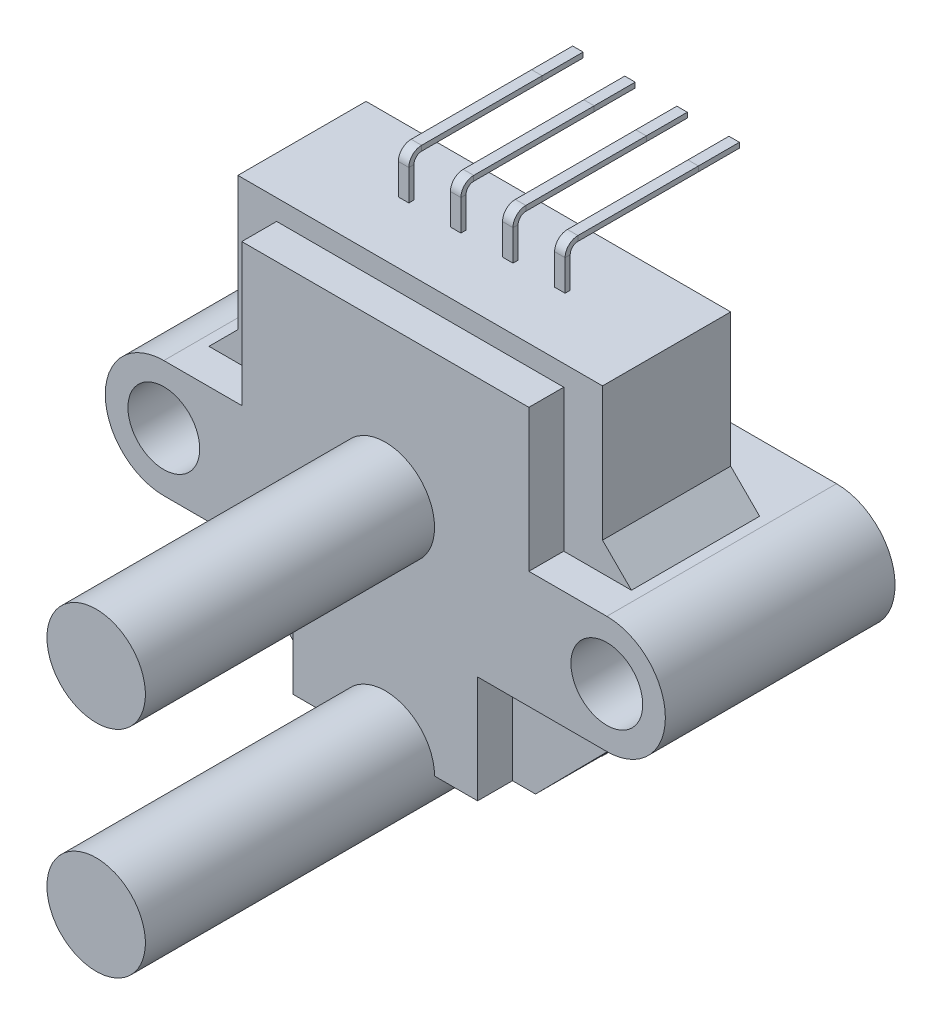
SolidWorks part; units mm, degrees
ref_plane "Front Plane" through (0, 0, 0) normal (0, 0, 1) x (1, 0, 0)
ref_plane "Top Plane" through (0, 0, 0) normal (0, 1, 0) x (1, 0, 0)
ref_plane "Right Plane" through (0, 0, 0) normal (1, 0, 0) x (0, 0, -1)
sketch "Sketch1" plane through (0, 0, 0) normal (0, 0, -1) x (1, 0, 0)
  line L0 (-7.62, 0) -> (-5.08, 0) construction
  line L1 (-5.08, 0) -> (-2.54, 0) construction
  line L2 (-2.54, 0) -> (0, 0) construction
  line L3 (-12.7, 2) -> (5.08, 2)
  line L4 (-3.81, 0) -> (-3.81, 2) construction
  line L5 (-3.81, 2) -> (-3.81, 12.78) construction
  line L6 (-14.61, 12.78) -> (6.99, 12.78) construction
  line L7 (-14.61, 12.78) -> (6.99, 12.78) construction
  line L8 (-14.61, 15.635) -> (6.99, 15.635)
  line L9 (-14.61, 9.925) -> (6.99, 9.925)
  line L10 (5.08, 2) -> (5.08, 8.515)
  line L11 (5.08, 8.515) -> (6.49, 9.925)
  line L12 (6.99, 15.635) -> (-0.9654, 23.6822)
  line L13 (-6.6546, 23.6822) -> (-14.61, 15.635)
  line L14 (-3.81, 12.78) -> (-3.81, 24.87) construction
  line L15 (-12.7, 8.515) -> (-14.11, 9.925)
  line L16 (-12.7, 2) -> (-12.7, 8.515)
  line L17 (-3.81, 20.87) -> (-3.81, 10.37) construction
  line L18 (0.19, 20.87) -> (0.19, 10.37)
  line L19 (-7.81, 20.87) -> (-7.81, 10.37)
  line L20 (-9.4347, 20.87) -> (1.8147, 20.87)
  circle A0 centre (-14.61, 12.78) radius 1.75
  circle A1 centre (6.99, 12.78) radius 1.75
  arc A2 (-14.61, 15.635) -> (-14.61, 9.925) centre (-14.61, 12.78) ccw
  arc A3 (6.99, 9.925) -> (6.99, 15.635) centre (6.99, 12.78) ccw
  arc A4 (-0.9654, 23.6822) -> (-6.6546, 23.6822) centre (-3.81, 20.87) ccw
  circle A5 centre (-3.81, 20.87) radius 2.4
  circle A6 centre (-3.81, 10.37) radius 2.4
  arc A7 (0.19, 20.87) -> (-7.81, 20.87) centre (-3.81, 20.87) ccw
  arc A8 (-7.81, 10.37) -> (0.19, 10.37) centre (-3.81, 10.37) ccw
  point P0 (0, 0)
  point P1 (-5.08, 0)
  point P3 (-2.54, 0)
  point P4 (0, 0)
  point P17 (-3.81, 12.78)
  point P19 (-3.81, 12.78)
  point P34 (-3.81, 15.62)
  dimension "D3" = 3.5
  dimension "D5" = 27.31
  dimension "D11" = 4
  dimension "D12" = 4.8
  dimension "D1" = 2.54
  dimension "D2" = 2
  dimension "D4" = 21.6
  dimension "D6" = 22.87
  dimension "D7" = 12.09
  dimension "D8" = 17.78
  dimension "D9" = 135
  dimension "D10" = 0.5
  dimension "D13" = 10.5
extrude "Boss-Extrude1" add sketch "Sketch1" against normal blind 3.25 contours L9 A8 L18 L8 A3 A1 | A8 L19 L8 L18 L9 | A7 L18 L8 L19 A4 | A8 L9 | L19 A8 L9 A2 L8 A0 | A7 L20 A4 | A5 L20 | A5 L20 | A6 L9 | A6 L9 region at (-11.8365, -12.7798, 0) region at (4.2165, -12.7798, 0) region at (-3.81, -13.3075, 0) region at (-6.9768, -9.8379, 0) region at (-3.81, -11.1528, 0) region at (-3.81, -9.107, 0) region at (-3.81, -17.8119, 0) region at (-7.4272, -22.3561, 0) region at (-3.81, -21.8886, 0) region at (-3.81, -19.8514, 0)
extrude "Boss-Extrude3" add sketch "Sketch1<4>" against normal blind 6.25 from surface contours L18 A7 L12 L8 | L9 A8 L18 L8 A3 A1 | A7 L18 L8 L19 A4 | A8 L9 | A8 L19 L8 L18 L9 | L19 A8 L9 A2 L8 A0 | L13 A7 L19 L8 | L9 A8 L11 L10 L3 L16 L15 | A5 L20 | A6 L9 | A6 L9 region at (-3.81, -5.5809, 0) region at (-11.8365, -12.7798, 0) region at (4.2165, -12.7798, 0) region at (-3.81, -13.3075, 0) region at (-6.9768, -9.8379, 0) region at (-10.1811, -17.7165, 0) region at (-3.81, -11.1528, 0) region at (-3.81, -9.107, 0) region at (2.5611, -17.7165, 0) region at (-3.81, -17.8119, 0) region at (-3.81, -19.8514, 0) starting at face at (-3.81, -14.4425, 3.25)
sketch "Sketch1<4>" plane through (0, 0, 0) normal (0, 0, -1) x (1, 0, 0) same geometry as "Sketch1"
sketch "Sketch3" plane through (0, 0, 9.5) normal (0, 0, 1) x (1, 0, 0)
  line L0 (3.19, -3) -> (-10.81, -3)
  line L1 (-14.11, -9.925) -> (6.49, -9.925)
  line L2 (6.99, -15.635) -> (-14.61, -15.635)
  line L3 (-10.81, -3) -> (-10.81, -9.925)
  line L4 (3.19, -3) -> (3.19, -9.925)
  line L5 (-8.31, -20.87) -> (0.69, -20.87)
  line L6 (0.69, -20.87) -> (0.69, -15.635)
  line L7 (-8.31, -20.87) -> (-8.31, -15.635)
  line L8 (-3.81, -2) -> (-3.81, -12.78) construction
  line L9 (6.49, -9.925) -> (5.08, -8.515)
  line L10 (5.08, -8.515) -> (5.08, -2)
  line L11 (5.08, -2) -> (-12.7, -2)
  line L12 (-12.7, -2) -> (-12.7, -8.515)
  line L13 (-12.7, -8.515) -> (-14.11, -9.925)
  line L14 (-14.11, -9.925) -> (-14.61, -9.925)
  line L15 (-14.61, -15.635) -> (-9.4347, -20.87)
  line L16 (1.8147, -20.87) -> (6.99, -15.635)
  line L17 (6.99, -9.925) -> (6.49, -9.925)
  line L18 (6.49, -9.925) -> (5.08, -8.515)
  line L19 (5.08, -8.515) -> (5.08, -2)
  line L20 (5.08, -2) -> (-12.7, -2)
  line L21 (-12.7, -2) -> (-12.7, -8.515)
  line L22 (-12.7, -8.515) -> (-14.11, -9.925)
  line L23 (-14.11, -9.925) -> (-14.61, -9.925)
  line L24 (-14.61, -15.635) -> (-9.4347, -20.87)
  line L25 (1.8147, -20.87) -> (6.99, -15.635)
  line L26 (6.99, -9.925) -> (6.49, -9.925)
  line L37 (-9.4347, -20.87) -> (1.8147, -20.87)
  line L38 (-9.4347, -20.87) -> (1.8147, -20.87)
  arc A3 (-14.61, -9.925) -> (-14.61, -15.635) centre (-14.61, -12.78) ccw
  arc A5 (6.99, -15.635) -> (6.99, -9.925) centre (6.99, -12.78) ccw
  arc A6 (-14.61, -9.925) -> (-14.61, -15.635) centre (-14.61, -12.78) ccw
  arc A8 (6.99, -15.635) -> (6.99, -9.925) centre (6.99, -12.78) ccw
  point P20 (-3.81, -3)
  circle M15 centre (6.99, -12.78) radius 1.75
  line M21 (-14.11, -9.925) -> (-14.61, -9.925)
  arc M22 (-14.61, -9.925) -> (-14.61, -15.635) centre (-14.61, -12.78) ccw
  arc M26 (6.99, -15.635) -> (6.99, -9.925) centre (6.99, -12.78) ccw
  line M27 (6.99, -9.925) -> (6.49, -9.925)
  circle M28 centre (-14.61, -12.78) radius 1.75
  dimension "D2" = 9
  dimension "D3" = 14
  dimension "D4" = 1
  dimension "D1" = 0
extrude "Boss-Extrude4" add sketch "Sketch3" along normal blind 1.7 contours L7 L5 L6 L2 | L2 L1 M26 M27 M21 M22 M28 M15 | L4 L0 L3 L1 region at (-3.81, -6.4625, 9.5) region at (-3.81, -12.78, 9.5) region at (-3.81, -18.2525, 9.5)
extrude "Boss-Extrude5" add sketch "Sketch1<5>" against normal blind 25.3 contours A5 | A6
sketch "Sketch1<5>" plane through (0, 0, 0) normal (0, 0, -1) x (1, 0, 0) same geometry as "Sketch1"
sketch "Sketch4" plane through (0, 0, 0) normal (1, 0, 0) x (0, 0, -1)
  line L0 (0, 0) -> (-5.875, 0)
  line L1 (-6.375, -0.5) -> (-6.375, -2)
  line L2 (-9.5, -2) -> (-3.25, -2) construction
  line L3 (0, 0) -> (2, 0)
  arc A0 (-5.875, 0) -> (-6.375, -0.5) centre (-5.875, -0.5) ccw
  dimension "D1" = 0.5
  dimension "D2" = 2
sketch "Sketch5" plane through (0, -2, 0) normal (0, 1, 0) x (1, 0, 0)
  line L1 (-0.255, -6.25) -> (0.255, -6.25)
  line L2 (-0.255, -6.25) -> (-0.255, -6.5)
  line L3 (-0.255, -6.5) -> (0.255, -6.5)
  line L4 (0.255, -6.25) -> (0.255, -6.5)
  line L5 (-0.255, -6.25) -> (0.255, -6.5) construction
  line L6 (-0.255, -6.5) -> (0.255, -6.25) construction
  point P0 (0, -6.375)
  dimension "D1" = 0.51
  dimension "D2" = 0.25
sweep "Sweep1" add profiles "Sketch5" path "Sketch4"
pattern_linear "LPattern1" count 4 spacing 2.54 along (-1, 0, 0) of "Sweep1"
sketch "Sketch6" plane through (0, 0, -2) normal (0, 0, -1) x (-1, 0, 0)
  circle A0 centre (0, 0) radius 0.5
  dimension "D1" = 1
